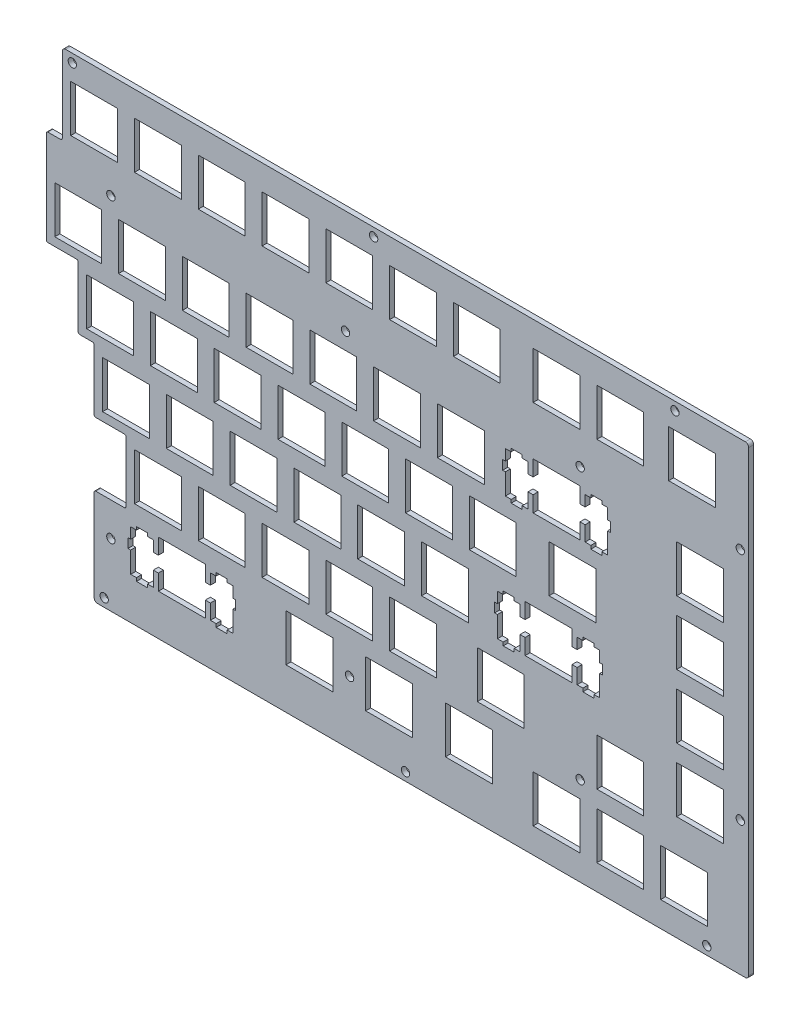
SolidWorks part; units mm, degrees
material "PC 高粘度"
ref_plane "前视基准面" through (0, 0, 0) normal (0, 0, 1) x (1, 0, 0)
ref_plane "上视基准面" through (0, 0, 0) normal (0, 1, 0) x (1, 0, 0)
ref_plane "右视基准面" through (0, 0, 0) normal (1, 0, 0) x (0, 0, -1)
other "Configuration Table"
sketch "Model" plane through (0, 0, 0) normal (0, 0, 1) x (1, 0, 0)
  line L0 (4.8569, 129.021) -> (204.883, 129.021)
  line L1 (204.883, 129.021) -> (204.883, 0.4341)
  line L2 (204.883, 0.4341) -> (14.3819, 0.4341)
  line L3 (21.3817, 112.498) -> (7.3822, 126.497) construction
  line L4 (145.495, 16.9595) -> (159.494, 16.9595)
  line L5 (159.494, 16.9595) -> (159.494, 2.96)
  line L6 (159.494, 2.96) -> (145.495, 2.96)
  line L7 (145.495, 2.96) -> (145.495, 16.9595)
  line L8 (164.545, 16.9595) -> (178.544, 16.9595)
  line L9 (178.544, 16.9595) -> (178.544, 2.96)
  line L10 (178.544, 2.96) -> (164.545, 2.96)
  line L11 (164.545, 2.96) -> (164.545, 16.9595)
  line L12 (183.595, 16.9595) -> (197.594, 16.9595)
  line L13 (197.594, 16.9595) -> (197.594, 2.96)
  line L14 (197.594, 2.96) -> (183.595, 2.96)
  line L15 (183.595, 2.96) -> (183.595, 16.9595)
  line L16 (33.5759, 21.722) -> (33.5759, 17.0215)
  line L17 (33.5759, 17.0215) -> (32.0504, 17.0215)
  line L18 (32.0504, 17.0215) -> (32.0504, 20.2517)
  line L19 (32.0504, 20.2517) -> (30.3251, 20.2517)
  line L20 (30.3251, 20.2517) -> (30.3251, 21.1722)
  line L21 (30.3251, 21.1722) -> (27.0261, 21.1722)
  line L22 (27.0261, 21.1722) -> (27.0261, 20.2517)
  line L23 (27.0261, 20.2517) -> (25.3008, 20.2517)
  line L24 (25.3008, 20.2517) -> (25.3008, 17.0215)
  line L25 (25.3008, 17.0215) -> (24.4753, 17.0215)
  line L26 (24.4753, 17.0215) -> (24.4753, 14.2227)
  line L27 (24.4753, 14.2227) -> (25.3008, 14.2227)
  line L28 (25.3008, 14.2227) -> (25.3008, 7.9527)
  line L29 (25.3008, 7.9527) -> (27.0261, 7.9527)
  line L30 (27.0261, 7.9527) -> (27.0261, 6.9729)
  line L31 (27.0261, 6.9729) -> (30.3251, 6.9729)
  line L32 (30.3251, 6.9729) -> (30.3251, 7.9527)
  line L33 (30.3251, 7.9527) -> (32.0504, 7.9527)
  line L34 (32.0504, 7.9527) -> (32.0504, 12.4216)
  line L35 (32.0504, 12.4216) -> (33.5759, 12.4216)
  line L36 (33.5759, 12.4216) -> (33.5759, 7.7225)
  line L37 (33.5759, 7.7225) -> (47.5753, 7.7225)
  line L38 (47.5753, 7.7225) -> (47.5753, 12.4216)
  line L39 (47.5753, 12.4216) -> (49.101, 12.4216)
  line L40 (49.101, 12.4216) -> (49.101, 7.9527)
  line L41 (49.101, 7.9527) -> (50.8247, 7.9527)
  line L42 (50.8247, 7.9527) -> (50.8247, 6.9729)
  line L43 (50.8247, 6.9729) -> (54.1253, 6.9729)
  line L44 (54.1253, 6.9729) -> (54.1253, 7.9527)
  line L45 (54.1253, 7.9527) -> (55.8504, 7.9527)
  line L46 (55.8504, 7.9527) -> (55.8504, 14.2227)
  line L47 (55.8504, 14.2227) -> (56.6759, 14.2227)
  line L48 (56.6759, 14.2227) -> (56.6759, 17.0215)
  line L49 (56.6759, 17.0215) -> (55.8504, 17.0215)
  line L50 (55.8504, 17.0215) -> (55.8504, 20.2517)
  line L51 (55.8504, 20.2517) -> (54.1253, 20.2517)
  line L52 (54.1253, 20.2517) -> (54.1253, 21.1722)
  line L53 (54.1253, 21.1722) -> (50.8247, 21.1722)
  line L54 (50.8247, 21.1722) -> (50.8247, 20.2517)
  line L55 (50.8247, 20.2517) -> (49.101, 20.2517)
  line L56 (49.101, 20.2517) -> (49.101, 17.0215)
  line L57 (49.101, 17.0215) -> (47.5753, 17.0215)
  line L58 (47.5753, 17.0215) -> (47.5753, 21.722)
  line L59 (47.5753, 21.722) -> (33.5759, 21.722)
  line L60 (71.676, 21.722) -> (85.6753, 21.722)
  line L61 (85.6753, 21.722) -> (85.6753, 7.7225)
  line L62 (85.6753, 7.7225) -> (71.676, 7.7225)
  line L63 (71.676, 7.7225) -> (71.676, 21.722)
  line L64 (95.4871, 21.722) -> (109.488, 21.722)
  line L65 (109.488, 21.722) -> (109.488, 7.7225)
  line L66 (109.488, 7.7225) -> (95.4871, 7.7225)
  line L67 (95.4871, 7.7225) -> (95.4871, 21.722)
  line L68 (119.301, 21.722) -> (133.3, 21.722)
  line L69 (133.3, 21.722) -> (133.3, 7.7225)
  line L70 (133.3, 7.7225) -> (119.301, 7.7225)
  line L71 (119.301, 7.7225) -> (119.301, 21.722)
  line L72 (164.545, 36.0094) -> (178.544, 36.0094)
  line L73 (178.544, 36.0094) -> (178.544, 22.01)
  line L74 (178.544, 22.01) -> (164.545, 22.01)
  line L75 (164.545, 22.01) -> (164.545, 36.0094)
  line L76 (26.4322, 40.7719) -> (40.4315, 40.7719)
  line L77 (40.4315, 40.7719) -> (40.4315, 26.7725)
  line L78 (40.4315, 26.7725) -> (26.4322, 26.7725)
  line L79 (26.4322, 26.7725) -> (26.4322, 40.7719)
  line L80 (45.4822, 40.7719) -> (59.4815, 40.7719)
  line L81 (59.4815, 40.7719) -> (59.4815, 26.7725)
  line L82 (59.4815, 26.7725) -> (45.4822, 26.7725)
  line L83 (45.4822, 26.7725) -> (45.4822, 40.7719)
  line L84 (64.5322, 40.7719) -> (78.5315, 40.7719)
  line L85 (78.5315, 40.7719) -> (78.5315, 26.7725)
  line L86 (78.5315, 26.7725) -> (64.5322, 26.7725)
  line L87 (64.5322, 26.7725) -> (64.5322, 40.7719)
  line L88 (83.5822, 40.7719) -> (97.5815, 40.7719)
  line L89 (97.5815, 40.7719) -> (97.5815, 26.7725)
  line L90 (97.5815, 26.7725) -> (83.5822, 26.7725)
  line L91 (83.5822, 26.7725) -> (83.5822, 40.7719)
  line L92 (102.632, 40.7719) -> (116.632, 40.7719)
  line L93 (116.632, 40.7719) -> (116.632, 26.7725)
  line L94 (116.632, 26.7725) -> (102.632, 26.7725)
  line L95 (102.632, 26.7725) -> (102.632, 40.7719)
  line L96 (128.826, 40.7719) -> (142.825, 40.7719)
  line L97 (142.825, 40.7719) -> (142.825, 26.7725)
  line L98 (142.825, 26.7725) -> (128.826, 26.7725)
  line L99 (128.826, 26.7725) -> (128.826, 40.7719)
  line L100 (188.357, 40.7719) -> (202.357, 40.7719)
  line L101 (202.357, 40.7719) -> (202.357, 26.7725)
  line L102 (202.357, 26.7725) -> (188.357, 26.7725)
  line L103 (188.357, 26.7725) -> (188.357, 40.7719)
  line L104 (143.112, 59.8219) -> (143.112, 55.1215)
  line L105 (143.112, 55.1215) -> (141.588, 55.1215)
  line L106 (141.588, 55.1215) -> (141.588, 58.3516)
  line L107 (141.588, 58.3516) -> (139.863, 58.3516)
  line L108 (139.863, 58.3516) -> (139.863, 59.2723)
  line L109 (139.863, 59.2723) -> (136.562, 59.2723)
  line L110 (136.562, 59.2723) -> (136.562, 58.3516)
  line L111 (136.562, 58.3516) -> (134.837, 58.3516)
  line L112 (134.837, 58.3516) -> (134.837, 55.1215)
  line L113 (134.837, 55.1215) -> (134.013, 55.1215)
  line L114 (134.013, 55.1215) -> (134.013, 52.3226)
  line L115 (134.013, 52.3226) -> (134.837, 52.3226)
  line L116 (134.837, 52.3226) -> (134.837, 46.0527)
  line L117 (134.837, 46.0527) -> (136.562, 46.0527)
  line L118 (136.562, 46.0527) -> (136.562, 45.0716)
  line L119 (136.562, 45.0716) -> (139.863, 45.0716)
  line L120 (139.863, 45.0716) -> (139.863, 46.0527)
  line L121 (139.863, 46.0527) -> (141.588, 46.0527)
  line L122 (141.588, 46.0527) -> (141.588, 50.5217)
  line L123 (141.588, 50.5217) -> (143.112, 50.5217)
  line L124 (143.112, 50.5217) -> (143.112, 45.8227)
  line L125 (143.112, 45.8227) -> (157.113, 45.8227)
  line L126 (157.113, 45.8227) -> (157.113, 50.5217)
  line L127 (157.113, 50.5217) -> (158.637, 50.5217)
  line L128 (158.637, 50.5217) -> (158.637, 46.0527)
  line L129 (158.637, 46.0527) -> (160.362, 46.0527)
  line L130 (160.362, 46.0527) -> (160.362, 45.0716)
  line L131 (160.362, 45.0716) -> (163.663, 45.0716)
  line L132 (163.663, 45.0716) -> (163.663, 46.0527)
  line L133 (163.663, 46.0527) -> (165.388, 46.0527)
  line L134 (165.388, 46.0527) -> (165.388, 52.3226)
  line L135 (165.388, 52.3226) -> (166.212, 52.3226)
  line L136 (166.212, 52.3226) -> (166.212, 55.1215)
  line L137 (166.212, 55.1215) -> (165.388, 55.1215)
  line L138 (165.388, 55.1215) -> (165.388, 58.3516)
  line L139 (165.388, 58.3516) -> (163.663, 58.3516)
  line L140 (163.663, 58.3516) -> (163.663, 59.2723)
  line L141 (163.663, 59.2723) -> (160.362, 59.2723)
  line L142 (160.362, 59.2723) -> (160.362, 58.3516)
  line L143 (160.362, 58.3516) -> (158.637, 58.3516)
  line L144 (158.637, 58.3516) -> (158.637, 55.1215)
  line L145 (158.637, 55.1215) -> (157.113, 55.1215)
  line L146 (157.113, 55.1215) -> (157.113, 59.8219)
  line L147 (157.113, 59.8219) -> (143.112, 59.8219)
  line L148 (16.9072, 59.8219) -> (30.9066, 59.8219)
  line L149 (30.9066, 59.8219) -> (30.9066, 45.8227)
  line L150 (30.9066, 45.8227) -> (16.9072, 45.8227)
  line L151 (16.9072, 45.8227) -> (16.9072, 59.8219)
  line L152 (35.9572, 59.8219) -> (49.9565, 59.8219)
  line L153 (49.9565, 59.8219) -> (49.9565, 45.8227)
  line L154 (49.9565, 45.8227) -> (35.9572, 45.8227)
  line L155 (35.9572, 45.8227) -> (35.9572, 59.8219)
  line L156 (55.0072, 59.8219) -> (69.0065, 59.8219)
  line L157 (69.0065, 59.8219) -> (69.0065, 45.8227)
  line L158 (69.0065, 45.8227) -> (55.0072, 45.8227)
  line L159 (55.0072, 45.8227) -> (55.0072, 59.8219)
  line L160 (74.0572, 59.8219) -> (88.0565, 59.8219)
  line L161 (88.0565, 59.8219) -> (88.0565, 45.8227)
  line L162 (88.0565, 45.8227) -> (74.0572, 45.8227)
  line L163 (74.0572, 45.8227) -> (74.0572, 59.8219)
  line L164 (93.1072, 59.8219) -> (107.107, 59.8219)
  line L165 (107.107, 59.8219) -> (107.107, 45.8227)
  line L166 (107.107, 45.8227) -> (93.1072, 45.8227)
  line L167 (93.1072, 45.8227) -> (93.1072, 59.8219)
  line L168 (112.157, 59.8219) -> (126.157, 59.8219)
  line L169 (126.157, 59.8219) -> (126.157, 45.8227)
  line L170 (126.157, 45.8227) -> (112.157, 45.8227)
  line L171 (112.157, 45.8227) -> (112.157, 59.8219)
  line L172 (188.357, 59.8219) -> (202.357, 59.8219)
  line L173 (202.357, 59.8219) -> (202.357, 45.8227)
  line L174 (202.357, 45.8227) -> (188.357, 45.8227)
  line L175 (188.357, 45.8227) -> (188.357, 59.8219)
  line L176 (12.1447, 78.8719) -> (26.1441, 78.8719)
  line L177 (26.1441, 78.8719) -> (26.1441, 64.8727)
  line L178 (26.1441, 64.8727) -> (12.1447, 64.8727)
  line L179 (12.1447, 64.8727) -> (12.1447, 78.8719)
  line L180 (31.1947, 78.8719) -> (45.194, 78.8719)
  line L181 (45.194, 78.8719) -> (45.194, 64.8727)
  line L182 (45.194, 64.8727) -> (31.1947, 64.8727)
  line L183 (31.1947, 64.8727) -> (31.1947, 78.8719)
  line L184 (50.2447, 78.8719) -> (64.244, 78.8719)
  line L185 (64.244, 78.8719) -> (64.244, 64.8727)
  line L186 (64.244, 64.8727) -> (50.2447, 64.8727)
  line L187 (50.2447, 64.8727) -> (50.2447, 78.8719)
  line L188 (69.2947, 78.8719) -> (83.294, 78.8719)
  line L189 (83.294, 78.8719) -> (83.294, 64.8727)
  line L190 (83.294, 64.8727) -> (69.2947, 64.8727)
  line L191 (69.2947, 64.8727) -> (69.2947, 78.8719)
  line L192 (88.3447, 78.8719) -> (102.344, 78.8719)
  line L193 (102.344, 78.8719) -> (102.344, 64.8727)
  line L194 (102.344, 64.8727) -> (88.3447, 64.8727)
  line L195 (88.3447, 64.8727) -> (88.3447, 78.8719)
  line L196 (107.395, 78.8719) -> (121.394, 78.8719)
  line L197 (121.394, 78.8719) -> (121.394, 64.8727)
  line L198 (121.394, 64.8727) -> (107.395, 64.8727)
  line L199 (107.395, 64.8727) -> (107.395, 78.8719)
  line L200 (126.445, 78.8719) -> (140.444, 78.8719)
  line L201 (140.444, 78.8719) -> (140.444, 64.8727)
  line L202 (140.444, 64.8727) -> (126.445, 64.8727)
  line L203 (126.445, 64.8727) -> (126.445, 78.8719)
  line L204 (150.257, 78.8719) -> (164.257, 78.8719)
  line L205 (164.257, 78.8719) -> (164.257, 64.8727)
  line L206 (164.257, 64.8727) -> (150.257, 64.8727)
  line L207 (150.257, 64.8727) -> (150.257, 78.8719)
  line L208 (188.357, 78.8719) -> (202.357, 78.8719)
  line L209 (202.357, 78.8719) -> (202.357, 64.8727)
  line L210 (202.357, 64.8727) -> (188.357, 64.8727)
  line L211 (188.357, 64.8727) -> (188.357, 78.8719)
  line L212 (145.493, 97.9219) -> (145.493, 93.2215)
  line L213 (145.493, 93.2215) -> (143.969, 93.2215)
  line L214 (143.969, 93.2215) -> (143.969, 96.4516)
  line L215 (143.969, 96.4516) -> (142.244, 96.4516)
  line L216 (142.244, 96.4516) -> (142.244, 97.3723)
  line L217 (142.244, 97.3723) -> (138.943, 97.3723)
  line L218 (138.943, 97.3723) -> (138.943, 96.4516)
  line L219 (138.943, 96.4516) -> (137.218, 96.4516)
  line L220 (137.218, 96.4516) -> (137.218, 93.2215)
  line L221 (137.218, 93.2215) -> (136.394, 93.2215)
  line L222 (136.394, 93.2215) -> (136.394, 90.4226)
  line L223 (136.394, 90.4226) -> (137.218, 90.4226)
  line L224 (137.218, 90.4226) -> (137.218, 84.1527)
  line L225 (137.218, 84.1527) -> (138.943, 84.1527)
  line L226 (138.943, 84.1527) -> (138.943, 83.1716)
  line L227 (138.943, 83.1716) -> (142.244, 83.1716)
  line L228 (142.244, 83.1716) -> (142.244, 84.1527)
  line L229 (142.244, 84.1527) -> (143.969, 84.1527)
  line L230 (143.969, 84.1527) -> (143.969, 88.6217)
  line L231 (143.969, 88.6217) -> (145.493, 88.6217)
  line L232 (145.493, 88.6217) -> (145.493, 83.9227)
  line L233 (145.493, 83.9227) -> (159.494, 83.9227)
  line L234 (159.494, 83.9227) -> (159.494, 88.6217)
  line L235 (159.494, 88.6217) -> (161.018, 88.6217)
  line L236 (161.018, 88.6217) -> (161.018, 84.1527)
  line L237 (161.018, 84.1527) -> (162.743, 84.1527)
  line L238 (162.743, 84.1527) -> (162.743, 83.1716)
  line L239 (162.743, 83.1716) -> (166.044, 83.1716)
  line L240 (166.044, 83.1716) -> (166.044, 84.1527)
  line L241 (166.044, 84.1527) -> (167.768, 84.1527)
  line L242 (167.768, 84.1527) -> (167.768, 90.4226)
  line L243 (167.768, 90.4226) -> (168.593, 90.4226)
  line L244 (168.593, 90.4226) -> (168.593, 93.2215)
  line L245 (168.593, 93.2215) -> (167.768, 93.2215)
  line L246 (167.768, 93.2215) -> (167.768, 96.4516)
  line L247 (167.768, 96.4516) -> (166.044, 96.4516)
  line L248 (166.044, 96.4516) -> (166.044, 97.3723)
  line L249 (166.044, 97.3723) -> (162.743, 97.3723)
  line L250 (162.743, 97.3723) -> (162.743, 96.4516)
  line L251 (162.743, 96.4516) -> (161.018, 96.4516)
  line L252 (161.018, 96.4516) -> (161.018, 93.2215)
  line L253 (161.018, 93.2215) -> (159.494, 93.2215)
  line L254 (159.494, 93.2215) -> (159.494, 97.9219)
  line L255 (159.494, 97.9219) -> (145.493, 97.9219)
  line L256 (2.6197, 97.9219) -> (16.6192, 97.9219)
  line L257 (16.6192, 97.9219) -> (16.6192, 83.9227)
  line L258 (16.6192, 83.9227) -> (2.6197, 83.9227)
  line L259 (2.6197, 83.9227) -> (2.6197, 97.9219)
  line L260 (21.6697, 97.9219) -> (35.669, 97.9219)
  line L261 (35.669, 97.9219) -> (35.669, 83.9227)
  line L262 (35.669, 83.9227) -> (21.6697, 83.9227)
  line L263 (21.6697, 83.9227) -> (21.6697, 97.9219)
  line L264 (40.7197, 97.9219) -> (54.719, 97.9219)
  line L265 (54.719, 97.9219) -> (54.719, 83.9227)
  line L266 (54.719, 83.9227) -> (40.7197, 83.9227)
  line L267 (40.7197, 83.9227) -> (40.7197, 97.9219)
  line L268 (59.7697, 97.9219) -> (73.769, 97.9219)
  line L269 (73.769, 97.9219) -> (73.769, 83.9227)
  line L270 (73.769, 83.9227) -> (59.7697, 83.9227)
  line L271 (59.7697, 83.9227) -> (59.7697, 97.9219)
  line L272 (78.8197, 97.9219) -> (92.819, 97.9219)
  line L273 (92.819, 97.9219) -> (92.819, 83.9227)
  line L274 (92.819, 83.9227) -> (78.8197, 83.9227)
  line L275 (78.8197, 83.9227) -> (78.8197, 97.9219)
  line L276 (97.8683, 97.9219) -> (111.869, 97.9219)
  line L277 (111.869, 97.9219) -> (111.869, 83.9227)
  line L278 (111.869, 83.9227) -> (97.8683, 83.9227)
  line L279 (97.8683, 83.9227) -> (97.8683, 97.9219)
  line L280 (116.918, 97.9219) -> (130.919, 97.9219)
  line L281 (130.919, 97.9219) -> (130.919, 83.9227)
  line L282 (130.919, 83.9227) -> (116.918, 83.9227)
  line L283 (116.918, 83.9227) -> (116.918, 97.9219)
  line L284 (188.357, 97.9219) -> (202.357, 97.9219)
  line L285 (202.357, 97.9219) -> (202.357, 83.9227)
  line L286 (202.357, 83.9227) -> (188.357, 83.9227)
  line L287 (188.357, 83.9227) -> (188.357, 97.9219)
  line L288 (7.3822, 126.497) -> (21.3817, 126.497)
  line L289 (21.3817, 126.497) -> (21.3817, 112.498)
  line L290 (21.3817, 112.498) -> (7.3822, 112.498)
  line L291 (7.3822, 112.498) -> (7.3822, 126.497)
  line L292 (26.4322, 126.497) -> (40.4315, 126.497)
  line L293 (40.4315, 126.497) -> (40.4315, 112.498)
  line L294 (40.4315, 112.498) -> (26.4322, 112.498)
  line L295 (26.4322, 112.498) -> (26.4322, 126.497)
  line L296 (45.4822, 126.497) -> (59.4815, 126.497)
  line L297 (59.4815, 126.497) -> (59.4815, 112.498)
  line L298 (59.4815, 112.498) -> (45.4822, 112.498)
  line L299 (45.4822, 112.498) -> (45.4822, 126.497)
  line L300 (64.5322, 126.497) -> (78.5315, 126.497)
  line L301 (78.5315, 126.497) -> (78.5315, 112.498)
  line L302 (78.5315, 112.498) -> (64.5322, 112.498)
  line L303 (64.5322, 112.498) -> (64.5322, 126.497)
  line L304 (83.5822, 126.497) -> (97.5815, 126.497)
  line L305 (97.5815, 126.497) -> (97.5815, 112.498)
  line L306 (97.5815, 112.498) -> (83.5822, 112.498)
  line L307 (83.5822, 112.498) -> (83.5822, 126.497)
  line L308 (102.632, 126.497) -> (116.632, 126.497)
  line L309 (116.632, 126.497) -> (116.632, 112.498)
  line L310 (116.632, 112.498) -> (102.632, 112.498)
  line L311 (102.632, 112.498) -> (102.632, 126.497)
  line L312 (121.682, 126.497) -> (135.682, 126.497)
  line L313 (135.682, 126.497) -> (135.682, 112.498)
  line L314 (135.682, 112.498) -> (121.682, 112.498)
  line L315 (121.682, 112.498) -> (121.682, 126.497)
  line L316 (145.495, 126.497) -> (159.494, 126.497)
  line L317 (159.494, 126.497) -> (159.494, 112.498)
  line L318 (159.494, 112.498) -> (145.495, 112.498)
  line L319 (145.495, 112.498) -> (145.495, 126.497)
  line L320 (164.545, 126.497) -> (178.544, 126.497)
  line L321 (178.544, 126.497) -> (178.544, 112.498)
  line L322 (178.544, 112.498) -> (164.545, 112.498)
  line L323 (164.545, 112.498) -> (164.545, 126.497)
  line L324 (185.976, 126.497) -> (199.975, 126.497)
  line L325 (199.975, 126.497) -> (199.975, 112.498)
  line L326 (199.975, 112.498) -> (185.976, 112.498)
  line L327 (185.976, 112.498) -> (185.976, 126.497)
  line L328 (0.0939, 81.391) -> (0.0939, 109.971)
  line L329 (14.3819, 24.241) -> (14.3819, 0.4341)
  line L435 (0.0939, 109.971) -> (4.8569, 109.971)
  line L436 (4.8569, 109.971) -> (4.8569, 129.021)
  line L437 (0.0939, 81.391) -> (9.6189, 81.391)
  line L438 (9.6189, 81.391) -> (9.6189, 62.341)
  line L439 (9.6189, 62.341) -> (14.3819, 62.341)
  line L440 (14.3819, 62.341) -> (14.3819, 43.291)
  line L441 (14.3819, 43.291) -> (23.9069, 43.291)
  line L442 (23.9069, 43.291) -> (23.9069, 24.241)
  line L443 (23.9069, 24.241) -> (14.3819, 24.241)
  point P328 (14.3819, 119.4975)
  dimension "D1" = 19.05
  dimension "D2" = 4.763
  dimension "D3" = 28.58
  dimension "D4" = 9.525
  dimension "D5" = 9.525
extrude "凸台-拉伸1" add sketch "Model" along normal blind 1.5
sketch "草图1" plane through (0, 0, 1.5) normal (0, 0, 1) x (1, 0, 0)
  line L3 (14.3819, 0.4341) -> (204.883, 0.4341) construction
  line L4 (204.883, 0.4341) -> (204.883, 129.021) construction
  line L5 (204.883, 129.021) -> (4.8569, 129.021) construction
  line L6 (14.3819, -4.5659) -> (209.883, -4.5659)
  line L7 (209.883, -4.5659) -> (209.883, 134.021)
  line L8 (209.883, 134.021) -> (4.8569, 134.021)
  line L9 (14.3819, -4.5659) -> (209.883, -4.5659)
  line L10 (209.883, -4.5659) -> (209.883, 134.021)
  line L11 (209.883, 134.021) -> (4.8569, 134.021)
  line L12 (14.3819, 0.4341) -> (204.883, 0.4341)
  line L13 (204.883, 0.4341) -> (204.883, 129.021)
  line L14 (204.883, 129.021) -> (4.8569, 129.021)
  line L15 (4.8569, 129.021) -> (4.8569, 134.021)
  line L16 (14.3819, -4.5659) -> (14.3819, 0.4341)
  dimension "D1" = 5
extrude "凸台-拉伸2" add sketch "草图1" against normal blind 1.5
sketch "草图2" plane through (0, 0, 1.5) normal (0, 0, 1) x (1, 0, 0)
  line L0 (14.3819, -4.5659) -> (209.883, -4.5659) construction
  line L1 (14.3819, 24.241) -> (14.3819, -4.5659) construction
  line L2 (209.883, 134.021) -> (4.8569, 134.021) construction
  line L3 (4.8569, 134.021) -> (4.8569, 109.971) construction
  circle A0 centre (7.8569, 131.521) radius 1.25
  circle A1 centre (17.3819, -2.0659) radius 1.25
  dimension "D1" = 2.5
  dimension "D4" = 2.5
  dimension "D2" = 2.5
  dimension "D3" = 3
  dimension "D5" = 2.5
  dimension "D6" = 3
extrude "切除-拉伸1" cut sketch "草图2" against normal blind 3
fillet "圆角1" radius 1 4 edges at (14.3819, -4.5659, 0.75) (4.8569, 134.021, 0.75) (209.883, 134.021, 0.75) (209.883, -4.5659, 0.75)
pattern_linear "阵列(线性)1" count 3 spacing 90 along (1, 0, 0) of "切除-拉伸1"
sketch "草图3" plane through (0, 0, 1.5) normal (0, 0, 1) x (1, 0, 0)
  line L0 (209.883, -3.5659) -> (209.883, 133.021) construction
  line L1 (15.3819, -4.5659) -> (208.883, -4.5659) construction
  circle A0 centre (207.383, 35.4341) radius 1.25
  dimension "D1" = 2.5
  dimension "D2" = 2.5
  dimension "D3" = 40
extrude "切除-拉伸2" cut sketch "草图3" against normal blind 3
pattern_linear "阵列(线性)2" count 3 spacing 70 along (0, 1, 0) of "切除-拉伸2"
fillet "圆角2" radius 0.5 10 edges at (14.3819, 24.241, 0.75) (23.9069, 24.241, 0.75) (23.9069, 43.291, 0.75) (14.3819, 43.291, 0.75) (14.3819, 62.341, 0.75) (9.6189, 62.341, 0.75) (9.6189, 81.391, 0.75) (0.0939, 81.391, 0.75) (0.0939, 109.971, 0.75) (4.8569, 109.971, 0.75)
sketch "草图4" plane through (0, 0, 1.5) normal (0, 0, 1) x (1, 0, 0)
  line L0 (164.545, 36.0094) -> (164.545, 22.01) construction
  line L1 (19.3819, 102.9219) -> (159.545, 102.9219) construction
  line L2 (19.3819, 102.9219) -> (19.3819, 14.241) construction
  line L3 (19.3819, 14.241) -> (159.545, 14.241) construction
  line L4 (159.545, 102.9219) -> (159.545, 14.241) construction
  line L5 (14.3819, 23.741) -> (14.3819, -3.5659) construction
  line L6 (35.669, 97.9219) -> (21.6697, 97.9219) construction
  line L7 (23.4069, 24.241) -> (14.8819, 24.241) construction
  line L8 (159.494, 16.9595) -> (145.495, 16.9595) construction
  line L11 (85.6753, 7.7225) -> (85.6753, 21.722) construction
  circle A0 centre (19.3819, 102.9219) radius 1.25
  circle A1 centre (19.3819, 14.241) radius 1.25
  circle A2 centre (159.545, 21.9595) radius 1.25
  circle A3 centre (159.545, 102.9219) radius 1.25
  circle A4 centre (89.4635, 102.9219) radius 1.25
  circle A5 centre (90.6753, 14.241) radius 1.25
  dimension "D3" = 2.5
  dimension "D4" = 5
  dimension "D7" = 5
  dimension "D1" = 5
  dimension "D2" = 5
  dimension "D5" = 10
  dimension "D6" = 5
extrude "切除-拉伸3" cut sketch "草图4" against normal blind 10
